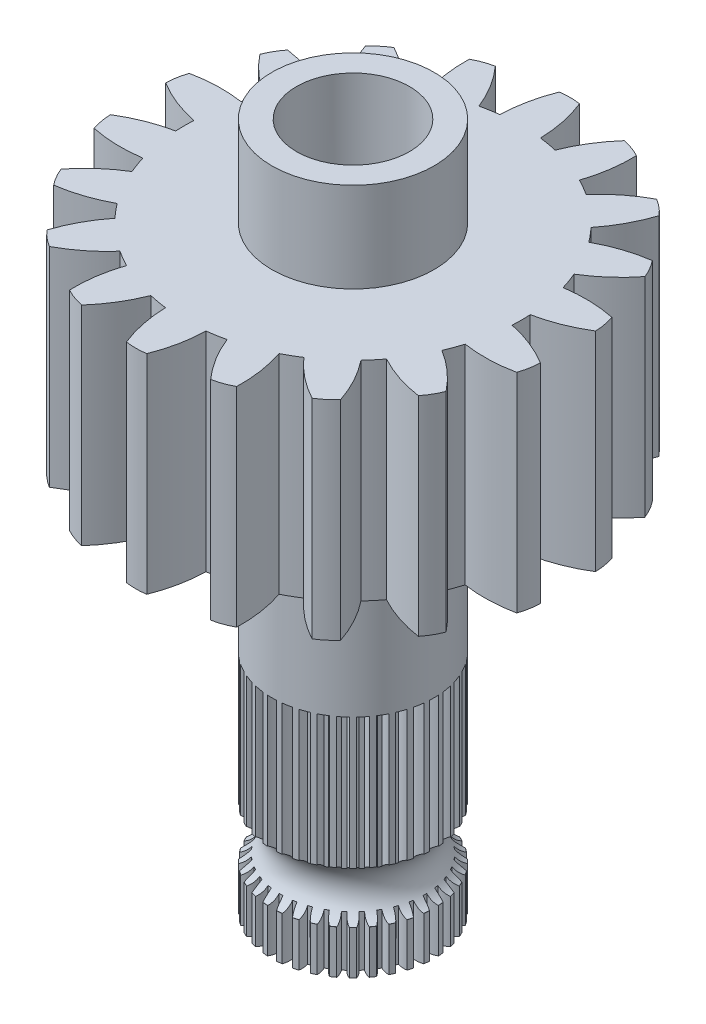
SolidWorks part; units mm, degrees
material "AISI 4130 Steel, annealed at 865C"
ref_plane "Front Plane" through (0, 0, 0) normal (0, 0, 1) x (1, 0, 0)
ref_plane "Top Plane" through (0, 0, 0) normal (0, 1, 0) x (1, 0, 0)
ref_plane "Right Plane" through (0, 0, 0) normal (1, 0, 0) x (0, 0, -1)
sketch "Sketch1" plane through (0, 0, 0) normal (0, 1, 0) x (1, 0, 0)
  circle A0 centre (0, 0) radius 21.15
  dimension "D1" = 42.3
extrude "Boss-Extrude1" add sketch "Sketch1" along normal blind 20.3
sketch "Sketch2" plane through (0, 20.3, 0) normal (0, 1, 0) x (1, 0, 0)
  circle A0 centre (0, 0) radius 7.9
  dimension "D1" = 15.8
extrude "Boss-Extrude2" add sketch "Sketch2" along normal blind 8.75
sketch "Sketch3" plane through (0, 0, 0) normal (0, -1, 0) x (1, 0, 0)
  circle A0 centre (0, 0) radius 7.9
  dimension "D1" = 15.8
extrude "Boss-Extrude3" add sketch "Sketch3" along normal blind 37.8
sketch "Sketch4" plane through (0, 0, 0) normal (0, -1, 0) x (1, 0, 0)
  line L3 (0, 21.15) -> (0, 16.4) construction
  arc A0 (1.9732, 16.2809) -> (-1.9732, 16.2809) centre (0, 0) ccw
  arc A3 (0.9888, 21.0727) -> (-0.9888, 21.0727) centre (0, 14.7904) ccw
  arc A4 (-0.9888, 21.0727) -> (-1.9732, 16.2809) centre (11.9241, 15.9228) ccw
  arc A5 (0.9888, 21.0727) -> (1.9732, 16.2809) centre (-11.9241, 15.9228) cw
  point P6 (0, 21.15)
sketch "Sketch5" plane through (0, 0, 0) normal (0, -1, 0) x (1, 0, 0)
  circle A0 centre (0, 0) radius 16.4
  circle A1 centre (0, 0) radius 21.15
extrude "Cut-Extrude2" cut sketch "Sketch5" against normal blind 27 contours A1 | A0
extrude "Boss-Extrude4" add sketch "Sketch4" against normal blind 20.3
pattern_circular "CirPattern1" count 18 over 360 about axis through (0, 0, 0) along (0, -1, 0) of "Boss-Extrude4"
sketch "Sketch6" plane through (0, 29.05, 0) normal (0, 1, 0) x (1, 0, 0)
  circle A0 centre (0, 0) radius 3.5
extrude "Cut-Extrude3" cut sketch "Sketch6" against normal blind 5
sketch "Sketch7" plane through (0, -37.8, 0) normal (0, -1, 0) x (1, 0, 0)
  line L0 (0, 7) -> (0, 7.9) construction
  arc A0 (0.4371, 7.8879) -> (-0.4371, 7.8879) centre (0, 0) ccw
  arc A1 (0.185, 6.9976) -> (-0.185, 6.9976) centre (0, 0) ccw
  arc A2 (0.4371, 7.8879) -> (0.185, 6.9976) centre (2.0908, 6.9389) ccw
  arc A3 (-0.4371, 7.8879) -> (-0.185, 6.9976) centre (-2.0908, 6.9389) cw
extrude "Cut-Extrude4" cut sketch "Sketch7" against normal blind 22
pattern_circular "CirPattern2" count 36 over 360 about axis through (0, -37.8, 0) along (0, -1, 0) of "Cut-Extrude4"
sketch "Sketch8" plane through (0, 0, 0) normal (0, 0, 1) x (1, 0, 0)
  line L1 (7.8879, -33.55) -> (7.844, -37.8) construction
  line L2 (7.844, -15.8) -> (7.844, -37.8) construction
  line L3 (7.8879, -15.8) -> (7.8879, -37.8) construction
  line L5 (7.8879, -33.55) -> (8.6413, -33.55)
  line L6 (8.6413, -33.55) -> (8.6413, -28.5503)
  line L7 (8.6413, -28.5503) -> (7.844, -28.5503)
  arc A1 (7.844, -28.5503) -> (7.8879, -33.55) centre (9.1535, -31.0388) ccw
  dimension "D1" = 4.9997
  dimension "D2" = 0.7534
  dimension "D3" = 4.25
ref_axis "Axis1" through (0, -41.1425, 0) along (0, 1, 0)
revolve "Cut-Revolve1" cut sketch "Sketch8" angle 360 about axis through (0, -41.1425, 0) along (0, 1, 0)
sketch "Sketch9" plane through (0, 29.05, 0) normal (0, 1, 0) x (1, 0, 0)
  circle A0 centre (0, 0) radius 5.5
extrude "Cut-Extrude5" cut sketch "Sketch9" against normal blind 14.5
sketch "Sketch10" plane through (0, 14.55, 0) normal (0, 1, 0) x (1, 0, 0)
  line L0 (0, 5.5) -> (0, -5.5) construction
  line L1 (-1.5, 5.2915) -> (-1.5, -5.2915)
  line L2 (1.5, 5.2915) -> (1.5, -5.2915)
  line L3 (1.5, 5.5) -> (1.5, -5.5) construction
  line L4 (-1.5, 5.5) -> (-1.5, -5.5) construction
  circle A0 centre (0, 0) radius 5.5 construction
  circle A3 centre (0, 0) radius 5.5
  circle A4 centre (0, 0) radius 5.5
  circle M4 centre (0, 0) radius 5.5
  dimension "D1" = 0
  dimension "D2" = 1.5
  dimension "D3" = 1.5
extrude "Boss-Extrude5" add sketch "Sketch10" along normal blind 3.5 contours L1 M4 | L2 M4 region at (-3.1635, 14.55, 0) region at (3.1635, 14.55, 0)
sketch "Sketch11" plane through (0, -37.8, 0) normal (0, -1, 0) x (1, 0, 0)
  circle A0 centre (0, 0) radius 5.5
extrude "Cut-Extrude6" cut sketch "Sketch11" against normal blind 51
